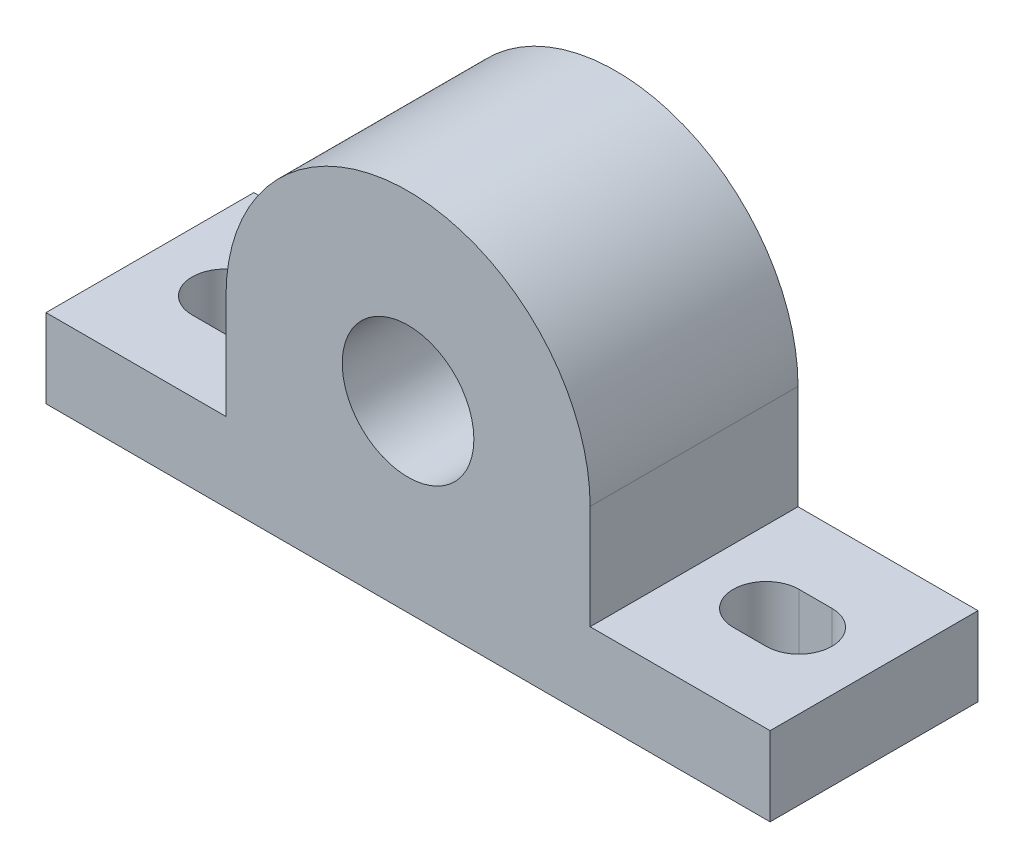
SolidWorks part; units mm, degrees
ref_plane "Front Plane" through (0, 0, 0) normal (0, 0, 1) x (1, 0, 0)
ref_plane "Top Plane" through (0, 0, 0) normal (0, 1, 0) x (1, 0, 0)
ref_plane "Right Plane" through (0, 0, 0) normal (1, 0, 0) x (0, 0, -1)
sketch "Sketch2" plane through (0, 0, 0) normal (0, 0, 1) x (1, 0, 0)
  line L0 (69.85, 0) -> (-69.85, 0)
  line L1 (-69.85, 0) -> (-69.85, 15.24)
  line L2 (-69.85, 15.24) -> (-35.1282, 15.24)
  line L3 (-35.1282, 15.24) -> (-35.1282, 35.3568)
  line L4 (0, 70.485) -> (36.4848, 70.485) construction
  line L5 (0, 0) -> (0, 70.485) construction
  line L6 (35.1282, 15.24) -> (35.1282, 35.3568)
  line L7 (69.85, 15.24) -> (35.1282, 15.24)
  line L8 (69.85, 0) -> (69.85, 15.24)
  arc A0 (-35.1282, 35.3568) -> (35.1282, 35.3568) centre (0, 35.3568) cw
  circle A1 centre (0, 35.3568) radius 12.7
  dimension "D5" = 25.4
  dimension "D1" = 15.24
  dimension "D2" = 69.85
  dimension "D3" = 34.7218
  dimension "D4" = 70.485
extrude "Boss-Extrude1" add sketch "Sketch2" along normal blind 40.1066
hole_wizard "1/2 (0.5) Diameter Slot1" positions "Sketch3" profile "Sketch4" size "1/2" standard "ANSI Inch" slot yes end condition through all
sketch "Sketch3" plane through (0, 15.24, 0) normal (0, 1, 0) x (1, 0, 0)
  line L1 (52.197, -20.0533) -> (52.197, 0) construction
  line L2 (69.85, 0) -> (35.1282, 0) construction
  line L4 (52.197, -20.0533) -> (52.197, -40.1066) construction
  line L5 (69.85, -40.1066) -> (35.1282, -40.1066) construction
  line L7 (0, 0) -> (0, -40.1066) construction
  line L8 (-35.1282, -40.1066) -> (35.1282, -40.1066) construction
  line L9 (61.722, -20.0533) -> (69.85, -20.0533) construction
  line L10 (69.85, -40.1066) -> (69.85, 0) construction
  line L11 (42.672, -20.0533) -> (61.722, -20.0533) construction
  point P0 (52.197, -20.0533)
  point P32 (0, 0)
  point P33 (-52.197, -20.0533)
  dimension "D2" = 8.128
sketch "Sketch4" plane through (52.197, 15.24, 20.0533) normal (1, 0, 0) x (0, 0, 1)
  line L0 (0, 0) -> (0, 15.24)
  line L1 (0, 15.24) -> (6.35, 15.24)
  line L2 (6.35, 15.24) -> (6.35, 0)
  line L5 (6.35, 0) -> (0, 0)
  line L11 (0, -6.35) -> (0, 107.95) construction
  dimension "Thru Hole Dia." = 12.7
  dimension "Thru Hole Depth" = 15.24
